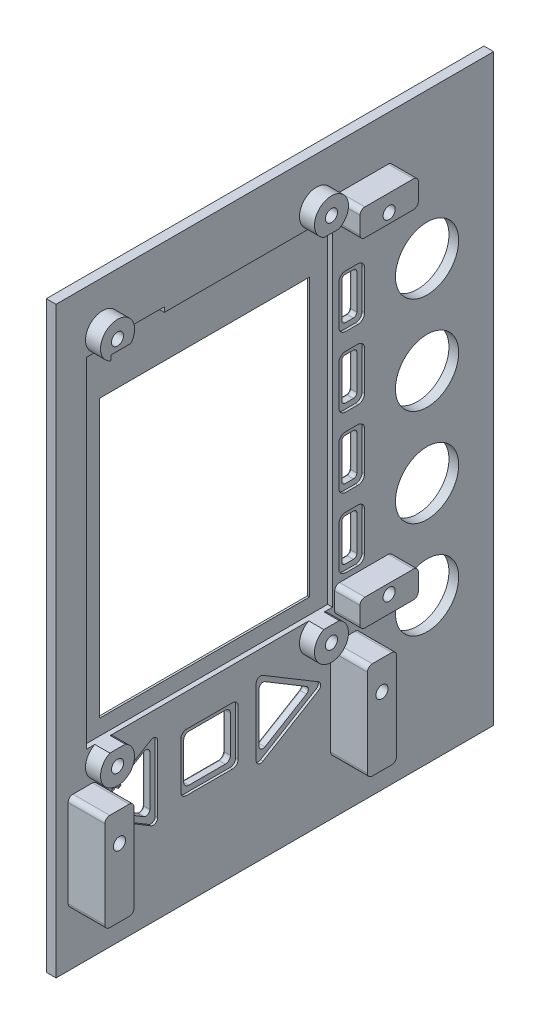
SolidWorks part; units mm, degrees
ref_plane "Front Plane" through (0, 0, 0) normal (0, 0, 1) x (1, 0, 0)
ref_plane "Top Plane" through (0, 0, 0) normal (0, 1, 0) x (1, 0, 0)
ref_plane "Right Plane" through (0, 0, 0) normal (1, 0, 0) x (0, 0, -1)
ref_plane "Plane2" through (-1175.0441, 0, 0) normal (-1, 0, 0) x (0, 0, 1)
sketch "Sketch2" plane through (-1175.0441, 0, 0) normal (-1, 0, 0) x (0, 0, 1)
  line L0 (-1294.1161, -887.0459) -> (-1294.1161, -787.0459) construction
  line L1 (-1209.1161, -777.0459) -> (-1299.1161, -777.0459)
  line L2 (-1209.1161, -777.0459) -> (-1209.1161, -897.0459)
  line L3 (-1209.1161, -897.0459) -> (-1299.1161, -897.0459)
  line L4 (-1299.1161, -777.0459) -> (-1299.1161, -897.0459)
  line L5 (-1294.1161, -887.0459) -> (-1292.6061, -887.0459) construction
  line L6 (-1294.1161, -787.0459) -> (-1292.6061, -787.0459) construction
  circle A0 centre (-1285.4211, -867.0459) radius 6.5
  circle A1 centre (-1285.4211, -847.0459) radius 6.5
  circle A2 centre (-1285.4211, -827.0459) radius 6.5
  circle A3 centre (-1285.4211, -807.0459) radius 6.5
  ellipse E0 centre (-1285.4211, -867.0459) end of major axis (-1284.9614, -867.5055) minor radius 0.65 construction
  ellipse E1 centre (-1285.4211, -847.0459) end of major axis (-1284.9614, -847.5055) minor radius 0.65 construction
  ellipse E2 centre (-1285.4211, -827.0459) end of major axis (-1284.9614, -827.5055) minor radius 0.65 construction
  ellipse E3 centre (-1285.4211, -807.0459) end of major axis (-1284.9614, -807.5055) minor radius 0.65 construction
  ellipse E4 centre (-1285.4211, -867.0459) end of major axis (-1284.9614, -867.5055) minor radius 0.65
  ellipse E5 centre (-1285.4211, -847.0459) end of major axis (-1284.9614, -847.5055) minor radius 0.65 construction
  ellipse E6 centre (-1285.4211, -827.0459) end of major axis (-1284.9614, -827.5055) minor radius 0.65
  ellipse E7 centre (-1285.4211, -807.0459) end of major axis (-1284.9614, -807.5055) minor radius 0.65
  dimension "D5" = 13
  dimension "D6" = 13
  dimension "D7" = 13
  dimension "D8" = 13
  dimension "D1" = 5
  dimension "D2" = 10
  dimension "D3" = 10
  dimension "D4" = 90
extrude "Boss-Extrude2" add sketch "Sketch2" along normal blind 2 contours L1 L4 L3 L2 A3 A2 A1 A0 region at (-1175.0441, -837.0459, -1252.4975)
sketch "Sketch3" plane through (-1177.0441, 0, 0) normal (-1, 0, 0) x (0, 0, 1)
  line L12 (-1219.0711, -856.2459) -> (-1262.2711, -856.2459) construction
  line L13 (-1262.2711, -856.2459) -> (-1262.2711, -799.2659) construction
  line L14 (-1219.0711, -799.2659) -> (-1219.0711, -856.2459) construction
  line L15 (-1262.2711, -799.2659) -> (-1219.0711, -799.2659) construction
  line L16 (-1219.0711, -856.2459) -> (-1262.2711, -856.2459)
  line L17 (-1262.2711, -856.2459) -> (-1262.2711, -799.2659)
  line L18 (-1219.0711, -799.2659) -> (-1219.0711, -856.2459)
  line L19 (-1262.2711, -799.2659) -> (-1219.0711, -799.2659)
extrude "tft_cutout" cut sketch "Sketch3" against normal through all
sketch "tft_inset_cutout" plane through (-1175.0441, 0, 0) normal (1, 0, 0) x (0, 0, -1)
  line L4 (1215.8711, -790.1248) -> (1215.8711, -858.9248) construction
  line L5 (1265.4711, -790.1248) -> (1215.8711, -790.1248) construction
  line L12 (1265.4711, -858.9248) -> (1265.4711, -790.1248) construction
  line L17 (1215.8711, -858.9248) -> (1265.4711, -858.9248) construction
  line L18 (1265.4711, -858.9248) -> (1265.4711, -790.1248) construction
  line L19 (1215.8711, -858.9248) -> (1265.4711, -858.9248) construction
  line L20 (1215.8711, -790.1248) -> (1215.8711, -858.9248) construction
  line L21 (1265.4711, -790.1248) -> (1215.8711, -790.1248) construction
  line L22 (1265.9711, -789.6248) -> (1215.3711, -789.6248)
  line L26 (1217.3711, -790.1248) -> (1231.3711, -790.1248)
  line L27 (1217.3711, -790.1248) -> (1217.3711, -788.6248)
  line L28 (1217.3711, -788.6248) -> (1231.3711, -788.6248)
  line L29 (1231.3711, -790.1248) -> (1231.3711, -788.6248)
  line L30 (1215.3711, -789.6248) -> (1215.3711, -859.4248)
  line L31 (1215.3711, -859.4248) -> (1265.9711, -859.4248)
  line L32 (1265.9711, -859.4248) -> (1265.9711, -789.6248)
  line M40 (1262.2711, -856.2459) -> (1219.0711, -856.2459)
  line M41 (1219.0711, -856.2459) -> (1219.0711, -799.2659)
  line M42 (1219.0711, -799.2659) -> (1262.2711, -799.2659)
  line M43 (1262.2711, -799.2659) -> (1262.2711, -856.2459)
  dimension "D3" = 1.5
  dimension "D4" = 0.5
  dimension "D1" = 14
  dimension "D2" = 1.5
extrude "Cut-Extrude2" cut sketch "tft_inset_cutout" against normal up to surface (1 mm away) contours L18 | L31 L32 L22 L29 L26 L27 L30 M43 M40 M41 M42 | L26 L29 L22 L27 | L22 L29 L28 L27 region at (-1175.0441, -824.5248, -1265.1089) region at (-1175.0441, -789.8748, -1224.3711) region at (-1175.0441, -789.1248, -1224.3711)
chamfer "Chamfer2" distance 1 angle 30 4 edges at (-1177.0441, -827.7559, -1262.2711) (-1177.0441, -856.2459, -1240.6711) (-1177.0441, -827.7559, -1219.0711) (-1177.0441, -799.2659, -1240.6711) first distance on face at (-1177.0441, -827.7559, -1240.6711)
sketch "Sketch6" plane through (-1175.0441, 0, 0) normal (1, 0, 0) x (0, 0, -1)
  line L5 (1266.4211, -861.2542) -> (1278.4211, -861.2542)
  line L6 (1266.4211, -861.2542) -> (1266.4211, -855.7542)
  line L7 (1266.4211, -855.7542) -> (1278.4211, -855.7542)
  line L8 (1266.4211, -861.2542) -> (1278.4211, -861.2542)
  line L9 (1278.4211, -861.2542) -> (1278.4211, -786.2542)
  line L10 (1278.4211, -786.2542) -> (1266.4211, -786.2542)
  line L11 (1266.4211, -786.2542) -> (1266.4211, -861.2542)
  line L12 (1266.4211, -861.2542) -> (1278.4211, -861.2542) construction
  line L13 (1278.4211, -861.2542) -> (1278.4211, -786.2542) construction
  line L14 (1278.4211, -786.2542) -> (1266.4211, -786.2542) construction
  line L15 (1266.4211, -786.2542) -> (1266.4211, -861.2542) construction
  line L16 (1278.4211, -861.2542) -> (1278.4211, -855.7542)
  line L17 (1266.4211, -786.2542) -> (1278.4211, -786.2542)
  line L18 (1266.4211, -786.2542) -> (1266.4211, -791.7542)
  line L19 (1266.4211, -791.7542) -> (1278.4211, -791.7542)
  line L20 (1278.4211, -786.2542) -> (1278.4211, -791.7542)
  circle A0 centre (1272.4211, -857.7542) radius 1.25 construction
  circle A1 centre (1272.4211, -857.7542) radius 1.25 construction
  circle A2 centre (1272.4211, -857.7542) radius 1.25
  circle A3 centre (1272.4211, -789.7542) radius 1.25 construction
  circle A4 centre (1272.4211, -789.7542) radius 1.25 construction
  circle A5 centre (1272.4211, -789.7542) radius 1.25
  dimension "D2" = 2.5
  dimension "D4" = 2.5
  dimension "D3" = 2
  dimension "D5" = 2
extrude "menu_standoffs" add sketch "Sketch6" along normal up to surface (5.203 mm away)
fillet "Fillet1" radius 1 8 edges at (-1172.4426, -791.7542, -1266.4211) (-1172.4426, -791.7542, -1278.4211) (-1172.4426, -786.2542, -1278.4211) (-1172.4426, -786.2542, -1266.4211) (-1172.4426, -855.7542, -1278.4211) (-1172.4426, -855.7542, -1266.4211) (-1172.4426, -861.2542, -1266.4211) (-1172.4426, -861.2542, -1278.4211)
sketch "Sketch7" plane through (-1169.8411, 0, 0) normal (1, 0, 0) x (0, 0, -1)
  circle A0 centre (1272.4211, -857.7542) radius 1.25 construction
  circle A1 centre (1272.4211, -789.7542) radius 1.25 construction
  circle A2 centre (1272.4211, -857.7542) radius 1.25
  circle A3 centre (1272.4211, -789.7542) radius 1.25
extrude "menu_standoff_holes" [suppressed] cut sketch "Sketch7" against normal blind 5 contours A2
sketch "Sketch8" plane through (-1175.0441, 0, 0) normal (1, 0, 0) x (0, 0, -1)
  circle A0 centre (1218.6711, -862.5459) radius 1.55 construction
  circle A1 centre (1262.6711, -862.5459) radius 1.55 construction
  circle A2 centre (1262.6711, -786.4659) radius 1.55 construction
  circle A3 centre (1218.6711, -786.4661) radius 1.55 construction
  circle A4 centre (1218.6711, -862.5459) radius 1.55 construction
  circle A5 centre (1262.6711, -862.5459) radius 1.55 construction
  circle A6 centre (1262.6711, -786.4659) radius 1.55 construction
  circle A7 centre (1218.6711, -786.4661) radius 1.55 construction
  circle A8 centre (1218.6711, -786.4661) radius 3.5
  circle A9 centre (1262.6711, -786.4659) radius 3.5
  circle A10 centre (1262.6711, -862.5459) radius 3.5
  circle A11 centre (1218.6711, -862.5459) radius 3.5
  circle A12 centre (1218.6711, -786.4661) radius 1.25
  circle A13 centre (1218.6711, -862.5459) radius 1.25
  circle A14 centre (1262.6711, -862.5459) radius 1.25
  circle A15 centre (1262.6711, -786.4659) radius 1.25
  dimension "D2" = 2.5
  dimension "D1" = 7
extrude "TFT_standoffs" add sketch "Sketch8" along normal up to surface (3.09 mm away)
sketch "Sketch9" plane through (-1175.0441, 0, 0) normal (1, 0, 0) x (0, 0, -1)
  circle A0 centre (1218.6711, -786.4661) radius 1.25 construction
  circle A1 centre (1218.6711, -862.5459) radius 1.25 construction
  circle A2 centre (1262.6711, -862.5459) radius 1.25 construction
  circle A3 centre (1262.6711, -786.4659) radius 1.25 construction
  circle A4 centre (1218.6711, -786.4661) radius 1.25
  circle A5 centre (1218.6711, -862.5459) radius 1.25
  circle A6 centre (1262.6711, -862.5459) radius 1.25
  circle A7 centre (1262.6711, -786.4659) radius 1.25
extrude "TFT_standoff_holes" cut sketch "Sketch9" against normal offset from surface (1 mm away) 1 up to face at (-1177.0441, -827.7559, -1240.6711)
extrude "Cut-Extrude5" cut sketch "Sketch5<3>" along normal through all contours L31 L32 L22 L29 L26 L27 L30 M43 M40 M41 M42 | L22 L29 L28 L27 | L26 L29 L22 L27 region at (-1175.0441, -824.5248, -1265.1089) region at (-1175.0441, -789.8748, -1224.3711) region at (-1175.0441, -789.1248, -1224.3711)
sketch "Sketch5<3>" plane through (-1175.0441, 0, 0) normal (1, 0, 0) x (0, 0, -1) same geometry as "tft_inset_cutout"
sketch "Sketch10" plane through (-1175.0441, 0, 0) normal (1, 0, 0) x (0, 0, -1)
  line L0 (1272.1746, -802.2609) -> (1272.1746, -810.2609) construction
  line L1 (1271.1746, -811.2609) -> (1268.6746, -811.2609) construction
  line L2 (1267.6746, -810.2609) -> (1267.6746, -802.2609) construction
  line L3 (1268.6746, -801.2609) -> (1271.1746, -801.2609) construction
  line L4 (1272.1746, -802.2609) -> (1272.1746, -810.2609) construction
  line L5 (1271.1746, -811.2609) -> (1268.6746, -811.2609) construction
  line L6 (1267.6746, -810.2609) -> (1267.6746, -802.2609) construction
  line L7 (1268.6746, -801.2609) -> (1271.1746, -801.2609) construction
  line L8 (1272.5746, -802.2609) -> (1272.5746, -810.2609)
  line L9 (1271.1746, -811.6609) -> (1268.6746, -811.6609)
  line L10 (1267.2746, -810.2609) -> (1267.2746, -802.2609)
  line L11 (1268.6746, -800.8609) -> (1271.1746, -800.8609)
  line L12 (1272.5746, -816.5909) -> (1272.5746, -824.5909)
  line L13 (1271.1746, -825.9909) -> (1268.6746, -825.9909)
  line L14 (1267.2746, -824.5909) -> (1267.2746, -816.5909)
  line L15 (1268.6746, -815.1909) -> (1271.1746, -815.1909)
  line L16 (1272.1746, -816.5909) -> (1272.1746, -824.5909) construction
  line L17 (1271.1746, -825.5909) -> (1268.6746, -825.5909) construction
  line L18 (1267.6746, -824.5909) -> (1267.6746, -816.5909) construction
  line L19 (1268.6746, -815.5909) -> (1271.1746, -815.5909) construction
  line L20 (1272.5746, -830.9209) -> (1272.5746, -838.9209)
  line L21 (1271.1746, -840.3209) -> (1268.6746, -840.3209)
  line L22 (1267.2746, -838.9209) -> (1267.2746, -830.9209)
  line L23 (1268.6746, -829.5209) -> (1271.1746, -829.5209)
  line L24 (1272.1746, -830.9209) -> (1272.1746, -838.9209) construction
  line L25 (1271.1746, -839.9209) -> (1268.6746, -839.9209) construction
  line L26 (1267.6746, -838.9209) -> (1267.6746, -830.9209) construction
  line L27 (1268.6746, -829.9209) -> (1271.1746, -829.9209) construction
  line L28 (1272.5746, -845.2509) -> (1272.5746, -853.2509)
  line L29 (1271.1746, -854.6509) -> (1268.6746, -854.6509)
  line L30 (1267.2746, -853.2509) -> (1267.2746, -845.2509)
  line L31 (1268.6746, -843.8509) -> (1271.1746, -843.8509)
  line L32 (1272.1746, -845.2509) -> (1272.1746, -853.2509) construction
  line L33 (1271.1746, -854.2509) -> (1268.6746, -854.2509) construction
  line L34 (1267.6746, -853.2509) -> (1267.6746, -845.2509) construction
  line L35 (1268.6746, -844.2509) -> (1271.1746, -844.2509) construction
  arc A0 (1272.1746, -802.2609) -> (1271.1746, -801.2609) centre (1271.1746, -802.2609) ccw construction
  arc A1 (1271.1746, -811.2609) -> (1272.1746, -810.2609) centre (1271.1746, -810.2609) ccw construction
  arc A2 (1267.6746, -810.2609) -> (1268.6746, -811.2609) centre (1268.6746, -810.2609) ccw construction
  arc A3 (1268.6746, -801.2609) -> (1267.6746, -802.2609) centre (1268.6746, -802.2609) ccw construction
  arc A4 (1272.1746, -802.2609) -> (1271.1746, -801.2609) centre (1271.1746, -802.2609) ccw construction
  arc A5 (1271.1746, -811.2609) -> (1272.1746, -810.2609) centre (1271.1746, -810.2609) ccw construction
  arc A6 (1267.6746, -810.2609) -> (1268.6746, -811.2609) centre (1268.6746, -810.2609) ccw construction
  arc A7 (1268.6746, -801.2609) -> (1267.6746, -802.2609) centre (1268.6746, -802.2609) ccw construction
  arc A8 (1271.1746, -811.6609) -> (1272.5746, -810.2609) centre (1271.1746, -810.2609) ccw
  arc A9 (1267.2746, -810.2609) -> (1268.6746, -811.6609) centre (1268.6746, -810.2609) ccw
  arc A10 (1268.6746, -800.8609) -> (1267.2746, -802.2609) centre (1268.6746, -802.2609) ccw
  arc A11 (1272.5746, -802.2609) -> (1271.1746, -800.8609) centre (1271.1746, -802.2609) ccw
  arc A12 (1271.1746, -825.9909) -> (1272.5746, -824.5909) centre (1271.1746, -824.5909) ccw
  arc A13 (1267.2746, -824.5909) -> (1268.6746, -825.9909) centre (1268.6746, -824.5909) ccw
  arc A14 (1268.6746, -815.1909) -> (1267.2746, -816.5909) centre (1268.6746, -816.5909) ccw
  arc A15 (1272.5746, -816.5909) -> (1271.1746, -815.1909) centre (1271.1746, -816.5909) ccw
  arc A16 (1272.1746, -816.5909) -> (1271.1746, -815.5909) centre (1271.1746, -816.5909) ccw construction
  arc A17 (1271.1746, -825.5909) -> (1272.1746, -824.5909) centre (1271.1746, -824.5909) ccw construction
  arc A18 (1267.6746, -824.5909) -> (1268.6746, -825.5909) centre (1268.6746, -824.5909) ccw construction
  arc A19 (1268.6746, -815.5909) -> (1267.6746, -816.5909) centre (1268.6746, -816.5909) ccw construction
  arc A20 (1271.1746, -840.3209) -> (1272.5746, -838.9209) centre (1271.1746, -838.9209) ccw
  arc A21 (1267.2746, -838.9209) -> (1268.6746, -840.3209) centre (1268.6746, -838.9209) ccw
  arc A22 (1268.6746, -829.5209) -> (1267.2746, -830.9209) centre (1268.6746, -830.9209) ccw
  arc A23 (1272.5746, -830.9209) -> (1271.1746, -829.5209) centre (1271.1746, -830.9209) ccw
  arc A24 (1272.1746, -830.9209) -> (1271.1746, -829.9209) centre (1271.1746, -830.9209) ccw construction
  arc A25 (1271.1746, -839.9209) -> (1272.1746, -838.9209) centre (1271.1746, -838.9209) ccw construction
  arc A26 (1267.6746, -838.9209) -> (1268.6746, -839.9209) centre (1268.6746, -838.9209) ccw construction
  arc A27 (1268.6746, -829.9209) -> (1267.6746, -830.9209) centre (1268.6746, -830.9209) ccw construction
  arc A28 (1271.1746, -854.6509) -> (1272.5746, -853.2509) centre (1271.1746, -853.2509) ccw
  arc A29 (1267.2746, -853.2509) -> (1268.6746, -854.6509) centre (1268.6746, -853.2509) ccw
  arc A30 (1268.6746, -843.8509) -> (1267.2746, -845.2509) centre (1268.6746, -845.2509) ccw
  arc A31 (1272.5746, -845.2509) -> (1271.1746, -843.8509) centre (1271.1746, -845.2509) ccw
  arc A32 (1272.1746, -845.2509) -> (1271.1746, -844.2509) centre (1271.1746, -845.2509) ccw construction
  arc A33 (1271.1746, -854.2509) -> (1272.1746, -853.2509) centre (1271.1746, -853.2509) ccw construction
  arc A34 (1267.6746, -853.2509) -> (1268.6746, -854.2509) centre (1268.6746, -853.2509) ccw construction
  arc A35 (1268.6746, -844.2509) -> (1267.6746, -845.2509) centre (1268.6746, -845.2509) ccw construction
  dimension "D1" = 0.4
  dimension "D2" = 4
extrude "menu_panel_inset" cut sketch "Sketch10" against normal offset from surface 1.5 and the other way through all up to face at (-1177.0441, -827.7559, -1240.6711)
sketch "Sketch11" plane through (-1177.0441, 0, 0) normal (-1, 0, 0) x (0, 0, 1)
  line L0 (-1270.7746, -810.2609) -> (-1269.0746, -810.2609) construction
  line L1 (-1271.1746, -802.6609) -> (-1271.1746, -809.8609) construction
  line L2 (-1270.7746, -802.2609) -> (-1269.0746, -802.2609) construction
  line L3 (-1268.6746, -802.6609) -> (-1268.6746, -809.8609) construction
  line L4 (-1270.7746, -810.2609) -> (-1269.0746, -810.2609) construction
  line L5 (-1271.1746, -802.6609) -> (-1271.1746, -809.8609) construction
  line L6 (-1270.7746, -802.2609) -> (-1269.0746, -802.2609) construction
  line L7 (-1268.6746, -802.6609) -> (-1268.6746, -809.8609) construction
  line L8 (-1268.3746, -802.6609) -> (-1268.3746, -809.8609)
  line L9 (-1270.7746, -810.5609) -> (-1269.0746, -810.5609)
  line L10 (-1271.4746, -802.6609) -> (-1271.4746, -809.8609)
  line L11 (-1270.7746, -801.9609) -> (-1269.0746, -801.9609)
  line L12 (-1268.3746, -816.9909) -> (-1268.3746, -824.1909)
  line L13 (-1270.7746, -824.8909) -> (-1269.0746, -824.8909)
  line L14 (-1271.4746, -816.9909) -> (-1271.4746, -824.1909)
  line L15 (-1270.7746, -816.2909) -> (-1269.0746, -816.2909)
  line L16 (-1270.7746, -824.5909) -> (-1269.0746, -824.5909) construction
  line L17 (-1271.1746, -816.9909) -> (-1271.1746, -824.1909) construction
  line L18 (-1270.7746, -816.5909) -> (-1269.0746, -816.5909) construction
  line L19 (-1268.6746, -816.9909) -> (-1268.6746, -824.1909) construction
  line L20 (-1268.3746, -831.3209) -> (-1268.3746, -838.5209)
  line L21 (-1270.7746, -839.2209) -> (-1269.0746, -839.2209)
  line L22 (-1271.4746, -831.3209) -> (-1271.4746, -838.5209)
  line L23 (-1270.7746, -830.6209) -> (-1269.0746, -830.6209)
  line L24 (-1270.7746, -838.9209) -> (-1269.0746, -838.9209) construction
  line L25 (-1271.1746, -831.3209) -> (-1271.1746, -838.5209) construction
  line L26 (-1270.7746, -830.9209) -> (-1269.0746, -830.9209) construction
  line L27 (-1268.6746, -831.3209) -> (-1268.6746, -838.5209) construction
  line L28 (-1268.3746, -845.6509) -> (-1268.3746, -852.8509)
  line L29 (-1270.7746, -853.5509) -> (-1269.0746, -853.5509)
  line L30 (-1271.4746, -845.6509) -> (-1271.4746, -852.8509)
  line L31 (-1270.7746, -844.9509) -> (-1269.0746, -844.9509)
  line L32 (-1270.7746, -853.2509) -> (-1269.0746, -853.2509) construction
  line L33 (-1271.1746, -845.6509) -> (-1271.1746, -852.8509) construction
  line L34 (-1270.7746, -845.2509) -> (-1269.0746, -845.2509) construction
  line L35 (-1268.6746, -845.6509) -> (-1268.6746, -852.8509) construction
  arc A0 (-1269.0746, -810.2609) -> (-1268.6746, -809.8609) centre (-1269.0746, -809.8609) ccw construction
  arc A1 (-1271.1746, -809.8609) -> (-1270.7746, -810.2609) centre (-1270.7746, -809.8609) ccw construction
  arc A2 (-1270.7746, -802.2609) -> (-1271.1746, -802.6609) centre (-1270.7746, -802.6609) ccw construction
  arc A3 (-1268.6746, -802.6609) -> (-1269.0746, -802.2609) centre (-1269.0746, -802.6609) ccw construction
  arc A4 (-1269.0746, -810.2609) -> (-1268.6746, -809.8609) centre (-1269.0746, -809.8609) ccw construction
  arc A5 (-1271.1746, -809.8609) -> (-1270.7746, -810.2609) centre (-1270.7746, -809.8609) ccw construction
  arc A6 (-1270.7746, -802.2609) -> (-1271.1746, -802.6609) centre (-1270.7746, -802.6609) ccw construction
  arc A7 (-1268.6746, -802.6609) -> (-1269.0746, -802.2609) centre (-1269.0746, -802.6609) ccw construction
  arc A8 (-1269.0746, -810.5609) -> (-1268.3746, -809.8609) centre (-1269.0746, -809.8609) ccw
  arc A9 (-1271.4746, -809.8609) -> (-1270.7746, -810.5609) centre (-1270.7746, -809.8609) ccw
  arc A10 (-1270.7746, -801.9609) -> (-1271.4746, -802.6609) centre (-1270.7746, -802.6609) ccw
  arc A11 (-1268.3746, -802.6609) -> (-1269.0746, -801.9609) centre (-1269.0746, -802.6609) ccw
  arc A12 (-1269.0746, -824.8909) -> (-1268.3746, -824.1909) centre (-1269.0746, -824.1909) ccw
  arc A13 (-1271.4746, -824.1909) -> (-1270.7746, -824.8909) centre (-1270.7746, -824.1909) ccw
  arc A14 (-1270.7746, -816.2909) -> (-1271.4746, -816.9909) centre (-1270.7746, -816.9909) ccw
  arc A15 (-1268.3746, -816.9909) -> (-1269.0746, -816.2909) centre (-1269.0746, -816.9909) ccw
  arc A16 (-1269.0746, -824.5909) -> (-1268.6746, -824.1909) centre (-1269.0746, -824.1909) ccw construction
  arc A17 (-1271.1746, -824.1909) -> (-1270.7746, -824.5909) centre (-1270.7746, -824.1909) ccw construction
  arc A18 (-1270.7746, -816.5909) -> (-1271.1746, -816.9909) centre (-1270.7746, -816.9909) ccw construction
  arc A19 (-1268.6746, -816.9909) -> (-1269.0746, -816.5909) centre (-1269.0746, -816.9909) ccw construction
  arc A20 (-1269.0746, -839.2209) -> (-1268.3746, -838.5209) centre (-1269.0746, -838.5209) ccw
  arc A21 (-1271.4746, -838.5209) -> (-1270.7746, -839.2209) centre (-1270.7746, -838.5209) ccw
  arc A22 (-1270.7746, -830.6209) -> (-1271.4746, -831.3209) centre (-1270.7746, -831.3209) ccw
  arc A23 (-1268.3746, -831.3209) -> (-1269.0746, -830.6209) centre (-1269.0746, -831.3209) ccw
  arc A24 (-1269.0746, -838.9209) -> (-1268.6746, -838.5209) centre (-1269.0746, -838.5209) ccw construction
  arc A25 (-1271.1746, -838.5209) -> (-1270.7746, -838.9209) centre (-1270.7746, -838.5209) ccw construction
  arc A26 (-1270.7746, -830.9209) -> (-1271.1746, -831.3209) centre (-1270.7746, -831.3209) ccw construction
  arc A27 (-1268.6746, -831.3209) -> (-1269.0746, -830.9209) centre (-1269.0746, -831.3209) ccw construction
  arc A28 (-1269.0746, -853.5509) -> (-1268.3746, -852.8509) centre (-1269.0746, -852.8509) ccw
  arc A29 (-1271.4746, -852.8509) -> (-1270.7746, -853.5509) centre (-1270.7746, -852.8509) ccw
  arc A30 (-1270.7746, -844.9509) -> (-1271.4746, -845.6509) centre (-1270.7746, -845.6509) ccw
  arc A31 (-1268.3746, -845.6509) -> (-1269.0746, -844.9509) centre (-1269.0746, -845.6509) ccw
  arc A32 (-1269.0746, -853.2509) -> (-1268.6746, -852.8509) centre (-1269.0746, -852.8509) ccw construction
  arc A33 (-1271.1746, -852.8509) -> (-1270.7746, -853.2509) centre (-1270.7746, -852.8509) ccw construction
  arc A34 (-1270.7746, -845.2509) -> (-1271.1746, -845.6509) centre (-1270.7746, -845.6509) ccw construction
  arc A35 (-1268.6746, -845.6509) -> (-1269.0746, -845.2509) centre (-1269.0746, -845.6509) ccw construction
  dimension "D1" = 0.3
  dimension "D2" = 4
extrude "menu_panel_cutout" cut sketch "Sketch11" against normal through all
fillet "Fillet2" radius 0.25 32 edges at (-1177.0441, -806.2609, -1268.3746) (-1177.0441, -810.3558, -1268.5796) (-1177.0441, -810.5609, -1269.9246) (-1177.0441, -810.3558, -1271.2696) (-1177.0441, -806.2609, -1271.4746) (-1177.0441, -802.1659, -1271.2696) (-1177.0441, -801.9609, -1269.9246) (-1177.0441, -824.8909, -1269.9246) (-1177.0441, -824.6858, -1271.2696) (-1177.0441, -820.5909, -1271.4746) (-1177.0441, -816.4959, -1271.2696) (-1177.0441, -816.2909, -1269.9246) (-1177.0441, -816.4959, -1268.5796) (-1177.0441, -820.5909, -1268.3746) (-1177.0441, -839.2209, -1269.9246) (-1177.0441, -839.0158, -1271.2696) (-1177.0441, -834.9209, -1271.4746) (-1177.0441, -830.8259, -1271.2696) (-1177.0441, -830.6209, -1269.9246) (-1177.0441, -830.8259, -1268.5796) (-1177.0441, -834.9209, -1268.3746) (-1177.0441, -849.2509, -1268.3746) (-1177.0441, -853.3458, -1268.5796) (-1177.0441, -853.5509, -1269.9246) (-1177.0441, -853.3458, -1271.2696) (-1177.0441, -849.2509, -1271.4746) (-1177.0441, -845.1559, -1271.2696) (-1177.0441, -844.9509, -1269.9246) (-1177.0441, -802.1659, -1268.5796) (-1177.0441, -824.6858, -1268.5796) (-1177.0441, -839.0158, -1268.5796) (-1177.0441, -845.1559, -1268.5796)
sketch "Sketch12" plane through (-1175.0441, 0, 0) normal (1, 0, 0) x (0, 0, -1)
  line L0 (1271.6008, -886.0459) -> (1211.6008, -886.0459) construction
  line L1 (1271.6008, -866.0459) -> (1265.6008, -866.0459)
  line L2 (1271.6008, -866.0459) -> (1271.6008, -886.0459)
  line L3 (1271.6008, -886.0459) -> (1265.6008, -886.0459)
  line L4 (1265.6008, -866.0459) -> (1265.6008, -886.0459)
  line L5 (1211.6008, -866.0459) -> (1271.6008, -866.0459) construction
  line L6 (1211.6008, -886.0459) -> (1217.6008, -886.0459)
  line L7 (1211.6008, -886.0459) -> (1211.6008, -866.0459)
  line L8 (1211.6008, -866.0459) -> (1217.6008, -866.0459)
  line L9 (1217.6008, -886.0459) -> (1217.6008, -866.0459)
  circle A0 centre (1268.6008, -872.0459) radius 1.25
  circle A1 centre (1214.6008, -872.0459) radius 1.25
  dimension "D2" = 2.5
  dimension "D4" = 2.5
  dimension "D1" = 6
  dimension "D3" = 6
extrude "selector_standoffs" add sketch "Sketch12" along normal up to surface (7.55 mm away)
fillet "Fillet3" radius 1 8 edges at (-1171.2691, -886.0459, -1271.6008) (-1171.2691, -866.0459, -1271.6008) (-1171.2691, -866.0459, -1265.6008) (-1171.2691, -886.0459, -1265.6008) (-1171.2691, -886.0459, -1217.6008) (-1171.2691, -886.0459, -1211.6008) (-1171.2691, -866.0459, -1211.6008) (-1171.2691, -866.0459, -1217.6008)
sketch "Sketch13" plane through (-1175.0441, 0, 0) normal (1, 0, 0) x (0, 0, -1)
  line L0 (1219.3225, -872.4817) -> (1227.8506, -877.5986) construction
  line L1 (1228.6079, -877.1699) -> (1228.6079, -866.936) construction
  line L2 (1227.8506, -866.5073) -> (1219.3225, -871.6242) construction
  line L3 (1236.1711, -868.303) -> (1236.1711, -875.803) construction
  line L4 (1236.9211, -876.553) -> (1244.4211, -876.553) construction
  line L5 (1244.4211, -867.553) -> (1236.9211, -867.553) construction
  line L6 (1245.1711, -875.803) -> (1245.1711, -868.303) construction
  line L7 (1260.9565, -871.6242) -> (1252.4283, -866.5073) construction
  line L8 (1251.6711, -866.936) -> (1251.6711, -877.1699) construction
  line L9 (1252.4283, -877.5986) -> (1260.9565, -872.4817) construction
  line L10 (1219.3225, -872.4817) -> (1227.8506, -877.5986) construction
  line L11 (1228.6079, -877.1699) -> (1228.6079, -866.936) construction
  line L12 (1227.8506, -866.5073) -> (1219.3225, -871.6242) construction
  line L13 (1236.1711, -868.303) -> (1236.1711, -875.803) construction
  line L14 (1236.9211, -876.553) -> (1244.4211, -876.553) construction
  line L15 (1244.4211, -867.553) -> (1236.9211, -867.553) construction
  line L16 (1245.1711, -875.803) -> (1245.1711, -868.303) construction
  line L17 (1260.9565, -871.6242) -> (1252.4283, -866.5073) construction
  line L18 (1251.6711, -866.936) -> (1251.6711, -877.1699) construction
  line L19 (1252.4283, -877.5986) -> (1260.9565, -872.4817) construction
  line L20 (1219.1681, -872.7389) -> (1227.6963, -877.8559)
  line L21 (1228.9079, -877.1699) -> (1228.9079, -866.936)
  line L22 (1227.6963, -866.2501) -> (1219.1681, -871.367)
  line L23 (1235.8711, -868.303) -> (1235.8711, -875.803)
  line L24 (1236.9211, -876.853) -> (1244.4211, -876.853)
  line L25 (1245.4711, -875.803) -> (1245.4711, -868.303)
  line L26 (1244.4211, -867.253) -> (1236.9211, -867.253)
  line L27 (1261.1108, -871.367) -> (1252.5827, -866.2501)
  line L28 (1251.3711, -866.936) -> (1251.3711, -877.1699)
  line L29 (1252.5827, -877.8559) -> (1261.1108, -872.7389)
  arc A0 (1219.3225, -871.6242) -> (1219.3225, -872.4817) centre (1219.5797, -872.053) ccw construction
  arc A1 (1227.8506, -877.5986) -> (1228.6079, -877.1699) centre (1228.1079, -877.1699) ccw construction
  arc A2 (1228.6079, -866.936) -> (1227.8506, -866.5073) centre (1228.1079, -866.936) ccw construction
  arc A3 (1236.9211, -867.553) -> (1236.1711, -868.303) centre (1236.9211, -868.303) ccw construction
  arc A4 (1236.1711, -875.803) -> (1236.9211, -876.553) centre (1236.9211, -875.803) ccw construction
  arc A5 (1244.4211, -876.553) -> (1245.1711, -875.803) centre (1244.4211, -875.803) ccw construction
  arc A6 (1245.1711, -868.303) -> (1244.4211, -867.553) centre (1244.4211, -868.303) ccw construction
  arc A7 (1260.9565, -872.4817) -> (1260.9565, -871.6242) centre (1260.6992, -872.053) ccw construction
  arc A8 (1252.4283, -866.5073) -> (1251.6711, -866.936) centre (1252.1711, -866.936) ccw construction
  arc A9 (1251.6711, -877.1699) -> (1252.4283, -877.5986) centre (1252.1711, -877.1699) ccw construction
  arc A10 (1219.3225, -871.6242) -> (1219.3225, -872.4817) centre (1219.5797, -872.053) ccw construction
  arc A11 (1227.8506, -877.5986) -> (1228.6079, -877.1699) centre (1228.1079, -877.1699) ccw construction
  arc A12 (1228.6079, -866.936) -> (1227.8506, -866.5073) centre (1228.1079, -866.936) ccw construction
  arc A13 (1236.9211, -867.553) -> (1236.1711, -868.303) centre (1236.9211, -868.303) ccw construction
  arc A14 (1236.1711, -875.803) -> (1236.9211, -876.553) centre (1236.9211, -875.803) ccw construction
  arc A15 (1244.4211, -876.553) -> (1245.1711, -875.803) centre (1244.4211, -875.803) ccw construction
  arc A16 (1245.1711, -868.303) -> (1244.4211, -867.553) centre (1244.4211, -868.303) ccw construction
  arc A17 (1260.9565, -872.4817) -> (1260.9565, -871.6242) centre (1260.6992, -872.053) ccw construction
  arc A18 (1252.4283, -866.5073) -> (1251.6711, -866.936) centre (1252.1711, -866.936) ccw construction
  arc A19 (1251.6711, -877.1699) -> (1252.4283, -877.5986) centre (1252.1711, -877.1699) ccw construction
  arc A20 (1227.6963, -877.8559) -> (1228.9079, -877.1699) centre (1228.1079, -877.1699) ccw
  arc A21 (1228.9079, -866.936) -> (1227.6963, -866.2501) centre (1228.1079, -866.936) ccw
  arc A22 (1219.1681, -871.367) -> (1219.1681, -872.7389) centre (1219.5797, -872.053) ccw
  arc A23 (1235.8711, -875.803) -> (1236.9211, -876.853) centre (1236.9211, -875.803) ccw
  arc A24 (1244.4211, -876.853) -> (1245.4711, -875.803) centre (1244.4211, -875.803) ccw
  arc A25 (1245.4711, -868.303) -> (1244.4211, -867.253) centre (1244.4211, -868.303) ccw
  arc A26 (1236.9211, -867.253) -> (1235.8711, -868.303) centre (1236.9211, -868.303) ccw
  arc A27 (1252.5827, -866.2501) -> (1251.3711, -866.936) centre (1252.1711, -866.936) ccw
  arc A28 (1251.3711, -877.1699) -> (1252.5827, -877.8559) centre (1252.1711, -877.1699) ccw
  arc A29 (1261.1108, -872.7389) -> (1261.1108, -871.367) centre (1260.6992, -872.053) ccw
  dimension "D1" = 0.3
  dimension "D2" = 0.3
  dimension "D3" = 0.3
extrude "Cut-Extrude6" cut sketch "Sketch13" against normal through all
fillet "Fillet4" radius 0.25 20 edges at (-1177.0441, -876.853, -1240.6711) (-1177.0441, -876.5454, -1236.1786) (-1177.0441, -872.053, -1235.8711) (-1177.0441, -867.5605, -1236.1786) (-1177.0441, -867.253, -1240.6711) (-1177.0441, -867.5605, -1245.1635) (-1177.0441, -872.053, -1245.4711) (-1177.0441, -866.2399, -1251.7769) (-1177.0441, -868.8085, -1256.8467) (-1177.0441, -872.053, -1261.4992) (-1177.0441, -875.2974, -1256.8467) (-1177.0441, -877.866, -1251.7769) (-1177.0441, -876.5454, -1245.1635) (-1177.0441, -872.053, -1251.3711) (-1177.0441, -875.2974, -1223.4322) (-1177.0441, -872.053, -1218.7797) (-1177.0441, -868.8085, -1223.4322) (-1177.0441, -866.2399, -1228.5021) (-1177.0441, -872.053, -1228.9079) (-1177.0441, -877.866, -1228.5021)
sketch "Sketch17" plane through (-1175.0441, 0, 0) normal (1, 0, 0) x (0, 0, -1)
  line L18 (1221.6293, -869.0739) -> (1217.3788, -871.6242) construction
  line L19 (1217.3788, -872.4817) -> (1221.6293, -875.032) construction
  line L20 (1221.5079, -874.8176) -> (1221.5079, -869.2883) construction
  line L21 (1229.6079, -878.936) -> (1229.6079, -865.1699) construction
  line L22 (1228.8506, -864.7411) -> (1221.7715, -868.9886) construction
  line L23 (1221.9002, -868.953) -> (1227.4579, -868.953) construction
  line L24 (1227.7079, -869.203) -> (1227.7079, -874.903) construction
  line L25 (1227.4579, -875.153) -> (1221.9002, -875.153) construction
  line L26 (1221.7715, -875.1173) -> (1228.8506, -879.3648) construction
  line L27 (1221.6293, -869.0739) -> (1217.3788, -871.6242) construction
  line L28 (1217.3788, -872.4817) -> (1221.6293, -875.032) construction
  line L29 (1221.5079, -874.8176) -> (1221.5079, -869.2883) construction
  line L30 (1229.6079, -878.936) -> (1229.6079, -865.1699) construction
  line L31 (1258.6497, -875.032) -> (1262.9001, -872.4817) construction
  line L32 (1262.9001, -871.6242) -> (1258.6497, -869.0739) construction
  line L33 (1258.7711, -869.2883) -> (1258.7711, -874.8176) construction
  line L34 (1250.6711, -865.1699) -> (1250.6711, -878.936) construction
  line L35 (1251.4283, -879.3648) -> (1258.5074, -875.1173) construction
  line L36 (1258.3788, -875.153) -> (1252.8211, -875.153) construction
  line L37 (1252.5711, -874.903) -> (1252.5711, -869.203) construction
  line L38 (1252.8211, -868.953) -> (1258.3788, -868.953) construction
  line L39 (1258.5074, -868.9886) -> (1251.4283, -864.7411) construction
  line L40 (1235.1711, -867.303) -> (1235.1711, -876.803) construction
  line L41 (1235.9211, -877.553) -> (1245.4211, -877.553) construction
  line L42 (1246.1711, -876.803) -> (1246.1711, -867.303) construction
  line L43 (1245.4211, -866.553) -> (1235.9211, -866.553) construction
  line L44 (1258.6497, -875.032) -> (1262.9001, -872.4817) construction
  line L45 (1262.9001, -871.6242) -> (1258.6497, -869.0739) construction
  line L46 (1258.7711, -869.2883) -> (1258.7711, -874.8176) construction
  line L47 (1250.6711, -865.1699) -> (1250.6711, -878.936) construction
  line L48 (1251.4283, -879.3648) -> (1258.5074, -875.1173) construction
  line L49 (1258.3788, -875.153) -> (1252.8211, -875.153) construction
  line L50 (1252.5711, -874.903) -> (1252.5711, -869.203) construction
  line L51 (1252.8211, -868.953) -> (1258.3788, -868.953) construction
  line L52 (1258.5074, -868.9886) -> (1251.4283, -864.7411) construction
  line L53 (1235.1711, -867.303) -> (1235.1711, -876.803) construction
  line L54 (1235.9211, -877.553) -> (1245.4211, -877.553) construction
  line L55 (1246.1711, -876.803) -> (1246.1711, -867.303) construction
  line L56 (1245.4211, -866.553) -> (1235.9211, -866.553) construction
  line L57 (1258.5074, -875.1173) -> (1258.6497, -875.032)
  line L58 (1258.6497, -869.0739) -> (1258.5074, -868.9886)
  line L59 (1228.8506, -864.7411) -> (1221.7715, -868.9886) construction
  line L60 (1221.9002, -868.953) -> (1227.4579, -868.953) construction
  line L61 (1227.7079, -869.203) -> (1227.7079, -874.903) construction
  line L62 (1227.4579, -875.153) -> (1221.9002, -875.153) construction
  line L63 (1221.7715, -875.1173) -> (1228.8506, -879.3648) construction
  line L64 (1221.6293, -869.0739) -> (1221.7715, -868.9886)
  line L65 (1221.7715, -875.1173) -> (1221.6293, -875.032)
  line L66 (1258.7132, -875.4603) -> (1258.8555, -875.375)
  line L67 (1258.8555, -868.7309) -> (1258.7132, -868.6456)
  line L68 (1221.8351, -869.4169) -> (1221.9773, -869.3316)
  line L69 (1221.9773, -874.7743) -> (1221.8351, -874.689)
  line L70 (1221.4235, -868.7309) -> (1217.173, -871.2812)
  line L71 (1217.173, -872.8247) -> (1221.4235, -875.375)
  line L72 (1221.9079, -874.745) -> (1221.9079, -869.3609)
  line L73 (1221.5657, -875.4603) -> (1228.6449, -879.7078)
  line L74 (1230.0079, -878.936) -> (1230.0079, -865.1699)
  line L75 (1228.6449, -864.3981) -> (1221.5657, -868.6456)
  line L76 (1258.8555, -875.375) -> (1263.1059, -872.8247)
  line L77 (1263.1059, -871.2812) -> (1258.8555, -868.7309)
  line L78 (1258.3711, -869.3609) -> (1258.3711, -874.745)
  line L79 (1258.7132, -868.6456) -> (1251.6341, -864.3981)
  line L80 (1250.2711, -865.1699) -> (1250.2711, -878.936)
  line L81 (1251.6341, -879.7078) -> (1258.7132, -875.4603)
  line L82 (1258.3424, -874.753) -> (1252.9711, -874.753)
  line L83 (1252.9711, -874.753) -> (1252.9711, -869.353)
  line L84 (1252.9711, -869.353) -> (1258.3424, -869.353)
  line L85 (1234.7711, -867.303) -> (1234.7711, -876.803)
  line L86 (1235.9211, -877.953) -> (1245.4211, -877.953)
  line L87 (1246.5711, -876.803) -> (1246.5711, -867.303)
  line L88 (1245.4211, -866.153) -> (1235.9211, -866.153)
  line L89 (1221.9366, -869.353) -> (1227.3079, -869.353)
  line L90 (1227.3079, -869.353) -> (1227.3079, -874.753)
  line L91 (1227.3079, -874.753) -> (1221.9366, -874.753)
  line L92 (1221.4235, -875.375) -> (1221.5657, -875.4603)
  line L93 (1221.5657, -868.6456) -> (1221.4235, -868.7309)
  arc A18 (1217.3788, -871.6242) -> (1217.3788, -872.4817) centre (1217.6361, -872.053) ccw construction
  arc A19 (1221.5079, -874.8176) -> (1221.6293, -875.032) centre (1221.7579, -874.8176) ccw construction
  arc A20 (1221.6293, -869.0739) -> (1221.5079, -869.2883) centre (1221.7579, -869.2883) ccw construction
  arc A21 (1229.6079, -865.1699) -> (1228.8506, -864.7411) centre (1229.1079, -865.1699) ccw construction
  arc A22 (1221.9002, -868.953) -> (1221.7715, -868.9886) centre (1221.9002, -869.203) ccw construction
  arc A23 (1227.7079, -869.203) -> (1227.4579, -868.953) centre (1227.4579, -869.203) ccw construction
  arc A24 (1227.4579, -875.153) -> (1227.7079, -874.903) centre (1227.4579, -874.903) ccw construction
  arc A25 (1221.7715, -875.1173) -> (1221.9002, -875.153) centre (1221.9002, -874.903) ccw construction
  arc A26 (1228.8506, -879.3648) -> (1229.6079, -878.936) centre (1229.1079, -878.936) ccw construction
  arc A27 (1262.9001, -872.4817) -> (1262.9001, -871.6242) centre (1262.6429, -872.053) ccw construction
  arc A28 (1258.7711, -869.2883) -> (1258.6497, -869.0739) centre (1258.5211, -869.2883) ccw construction
  arc A29 (1258.6497, -875.032) -> (1258.7711, -874.8176) centre (1258.5211, -874.8176) ccw construction
  arc A30 (1250.6711, -878.936) -> (1251.4283, -879.3648) centre (1251.1711, -878.936) ccw construction
  arc A31 (1258.3788, -875.153) -> (1258.5074, -875.1173) centre (1258.3788, -874.903) ccw construction
  arc A32 (1252.5711, -874.903) -> (1252.8211, -875.153) centre (1252.8211, -874.903) ccw construction
  arc A33 (1252.8211, -868.953) -> (1252.5711, -869.203) centre (1252.8211, -869.203) ccw construction
  arc A34 (1258.5074, -868.9886) -> (1258.3788, -868.953) centre (1258.3788, -869.203) ccw construction
  arc A35 (1251.4283, -864.7411) -> (1250.6711, -865.1699) centre (1251.1711, -865.1699) ccw construction
  arc A36 (1235.1711, -876.803) -> (1235.9211, -877.553) centre (1235.9211, -876.803) ccw construction
  arc A37 (1245.4211, -877.553) -> (1246.1711, -876.803) centre (1245.4211, -876.803) ccw construction
  arc A38 (1246.1711, -867.303) -> (1245.4211, -866.553) centre (1245.4211, -867.303) ccw construction
  arc A39 (1235.9211, -866.553) -> (1235.1711, -867.303) centre (1235.9211, -867.303) ccw construction
  arc A40 (1262.9001, -872.4817) -> (1262.9001, -871.6242) centre (1262.6429, -872.053) ccw construction
  arc A41 (1258.7711, -869.2883) -> (1258.6497, -869.0739) centre (1258.5211, -869.2883) ccw construction
  arc A42 (1258.6497, -875.032) -> (1258.7711, -874.8176) centre (1258.5211, -874.8176) ccw construction
  arc A43 (1250.6711, -878.936) -> (1251.4283, -879.3648) centre (1251.1711, -878.936) ccw construction
  arc A44 (1258.3788, -875.153) -> (1258.5074, -875.1173) centre (1258.3788, -874.903) ccw construction
  arc A45 (1252.5711, -874.903) -> (1252.8211, -875.153) centre (1252.8211, -874.903) ccw construction
  arc A46 (1252.8211, -868.953) -> (1252.5711, -869.203) centre (1252.8211, -869.203) ccw construction
  arc A47 (1258.5074, -868.9886) -> (1258.3788, -868.953) centre (1258.3788, -869.203) ccw construction
  arc A48 (1251.4283, -864.7411) -> (1250.6711, -865.1699) centre (1251.1711, -865.1699) ccw construction
  arc A49 (1235.1711, -876.803) -> (1235.9211, -877.553) centre (1235.9211, -876.803) ccw construction
  arc A50 (1245.4211, -877.553) -> (1246.1711, -876.803) centre (1245.4211, -876.803) ccw construction
  arc A51 (1246.1711, -867.303) -> (1245.4211, -866.553) centre (1245.4211, -867.303) ccw construction
  arc A52 (1235.9211, -866.553) -> (1235.1711, -867.303) centre (1235.9211, -867.303) ccw construction
  arc A53 (1217.3788, -871.6242) -> (1217.3788, -872.4817) centre (1217.6361, -872.053) ccw construction
  arc A54 (1221.5079, -874.8176) -> (1221.6293, -875.032) centre (1221.7579, -874.8176) ccw construction
  arc A55 (1221.6293, -869.0739) -> (1221.5079, -869.2883) centre (1221.7579, -869.2883) ccw construction
  arc A56 (1229.6079, -865.1699) -> (1228.8506, -864.7411) centre (1229.1079, -865.1699) ccw construction
  arc A57 (1221.9002, -868.953) -> (1221.7715, -868.9886) centre (1221.9002, -869.203) ccw construction
  arc A58 (1227.7079, -869.203) -> (1227.4579, -868.953) centre (1227.4579, -869.203) ccw construction
  arc A59 (1227.4579, -875.153) -> (1227.7079, -874.903) centre (1227.4579, -874.903) ccw construction
  arc A60 (1221.7715, -875.1173) -> (1221.9002, -875.153) centre (1221.9002, -874.903) ccw construction
  arc A61 (1228.8506, -879.3648) -> (1229.6079, -878.936) centre (1229.1079, -878.936) ccw construction
  arc A62 (1217.173, -871.2812) -> (1217.173, -872.8247) centre (1217.6361, -872.053) ccw
  arc A63 (1221.9079, -874.745) -> (1221.9079, -874.745) centre (1221.9079, -874.745) cw
  arc A64 (1221.9079, -869.3609) -> (1221.9079, -869.3609) centre (1221.9079, -869.3609) cw
  arc A65 (1228.6449, -879.7078) -> (1230.0079, -878.936) centre (1229.1079, -878.936) ccw
  arc A66 (1230.0079, -865.1699) -> (1228.6449, -864.3981) centre (1229.1079, -865.1699) ccw
  arc A67 (1263.1059, -872.8247) -> (1263.1059, -871.2812) centre (1262.6429, -872.053) ccw
  arc A68 (1258.3711, -869.3609) -> (1258.3711, -869.3609) centre (1258.3711, -869.3609) cw
  arc A69 (1258.3711, -874.745) -> (1258.3711, -874.745) centre (1258.3711, -874.745) cw
  arc A70 (1251.6341, -864.3981) -> (1250.2711, -865.1699) centre (1251.1711, -865.1699) ccw
  arc A71 (1250.2711, -878.936) -> (1251.6341, -879.7078) centre (1251.1711, -878.936) ccw
  arc A72 (1258.3424, -874.753) -> (1258.3424, -874.753) centre (1258.3424, -874.753) cw
  arc A73 (1252.9711, -874.753) -> (1252.9711, -874.753) centre (1252.9711, -874.753) ccw
  arc A74 (1252.9711, -869.353) -> (1252.9711, -869.353) centre (1252.9711, -869.353) ccw
  arc A75 (1258.3424, -869.353) -> (1258.3424, -869.353) centre (1258.3424, -869.353) cw
  arc A76 (1234.7711, -876.803) -> (1235.9211, -877.953) centre (1235.9211, -876.803) ccw
  arc A77 (1245.4211, -877.953) -> (1246.5711, -876.803) centre (1245.4211, -876.803) ccw
  arc A78 (1246.5711, -867.303) -> (1245.4211, -866.153) centre (1245.4211, -867.303) ccw
  arc A79 (1235.9211, -866.153) -> (1234.7711, -867.303) centre (1235.9211, -867.303) ccw
  arc A80 (1221.9366, -869.353) -> (1221.9366, -869.353) centre (1221.9366, -869.353) cw
  arc A81 (1227.3079, -869.353) -> (1227.3079, -869.353) centre (1227.3079, -869.353) ccw
  arc A82 (1227.3079, -874.753) -> (1227.3079, -874.753) centre (1227.3079, -874.753) ccw
  arc A83 (1221.9366, -874.753) -> (1221.9366, -874.753) centre (1221.9366, -874.753) cw
  dimension "D1" = 0.4
extrude "Cut-Extrude7" cut sketch "Sketch17" against normal offset from surface 1.5 and the other way blind 2 contours L74 A66 L75 L93 L70 A62 L71 L92 L73 A65 L90 L91 L69 L72 L68 L89 | L88 A79 L85 A76 L86 A77 L87 A78 | L80 A71 L81 L66 L76 A67 L77 L67 L79 A70 region at (-1175.0441, -872.053, -1254.9824) region at (-1175.0441, -868.8637, -1221.5999) region at (-1175.0441, -872.053, -1240.6711) up to face at (-1177.0441, -872.053, -1225.2575)
equation "\"R_BNC\"= 13"
equation "\"D8@Sketch2\"=\"R_BNC\""
equation "\"D7@Sketch2\"=\"R_BNC\""
equation "\"D6@Sketch2\"=\"R_BNC\""
equation "\"D5@Sketch2\"=\"R_BNC\""
equation "\"R_m3_TAP\"= 2.5"
equation "\"D2@Sketch6\"=\"R_m3_TAP\""
equation "\"D4@Sketch6\"=\"R_m3_TAP\""
equation "\"R_TFT_mount_outer\"= 7"
equation "\"D1@Sketch8\"=\"R_TFT_mount_outer\""
equation "\"D2@Sketch8\"=\"R_m3_TAP\""
equation "\"D2@Sketch12\"=\"R_m3_TAP\""
equation "\"D4@Sketch12\"=\"R_m3_TAP\""
